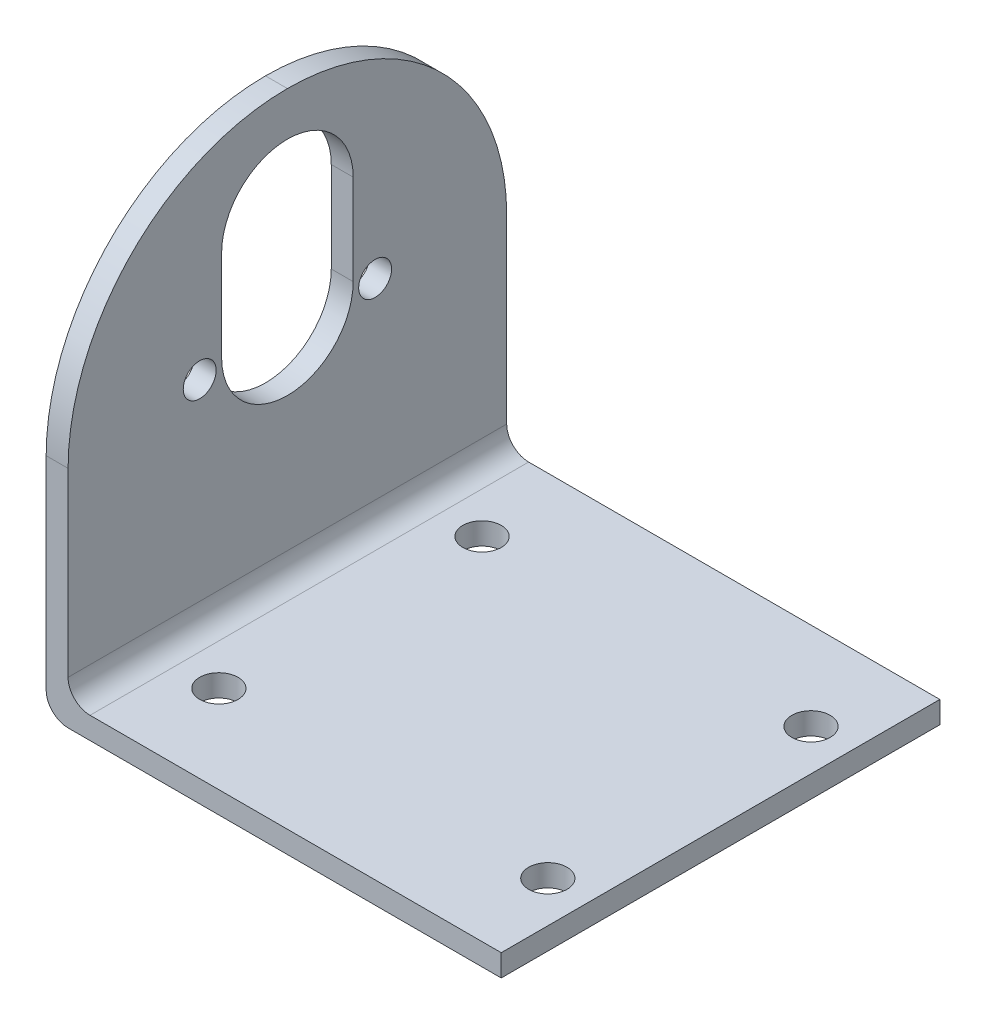
SolidWorks part; units mm, degrees
ref_plane "前视基准面" through (0, 0, 0) normal (0, 0, 1) x (1, 0, 0)
ref_plane "上视基准面" through (0, 0, 0) normal (0, 1, 0) x (1, 0, 0)
ref_plane "右视基准面" through (0, 0, 0) normal (1, 0, 0) x (0, 0, -1)
other "Configuration Table"
sketch "草图1" plane through (0, 0, 0) normal (0, 0, 1) x (1, 0, 0)
  line L0 (0, 38.5) -> (0, 2)
  line L1 (2, 0) -> (39.5, 0)
  line L2 (39.5, 0) -> (39.5, -2)
  line L3 (39.5, -2) -> (0, -2)
  line L4 (-2, 0) -> (-2, 38.5)
  line L5 (-2, 38.5) -> (0, 38.5)
  arc A0 (0, 2) -> (2, 0) centre (2, 2) ccw
  arc A1 (0, -2) -> (-2, 0) centre (0, 0) cw
  point P9 (0, 0)
  dimension "D5" = 2
  dimension "D1" = 2
  dimension "D2" = 41.5
  dimension "D3" = 2
  dimension "D4" = 40.5
extrude "凸台-拉伸1" add sketch "草图1" along normal blind 40
sketch "草图2" plane through (0, 0, 0) normal (0, 1, 0) x (1, 0, 0)
  line L0 (48.3574, -20) -> (-10.2137, -20) construction
  line L1 (20.75, 5.3835) -> (20.75, -45.303) construction
  line L2 (39.5, -40) -> (39.5, 0) construction
  line L3 (2, -40) -> (2, 0) construction
  line L4 (39.5, 0) -> (2, 0) construction
  line L5 (39.5, -40) -> (2, -40) construction
  circle A0 centre (5.75, -32) radius 1.75
  circle A1 centre (35.75, -32) radius 1.75
  circle A2 centre (5.75, -8) radius 1.75
  circle A3 centre (35.75, -8) radius 1.75
  dimension "D1" = 3.5
  dimension "D2" = 30
  dimension "D3" = 24
extrude "切除-拉伸1" cut sketch "草图2" against normal through all
sketch "草图3" plane through (0, 0, 0) normal (1, 0, 0) x (0, 0, -1)
  line L0 (-20, 43.5435) -> (-20, -10.4648) construction
  line L1 (12.7471, 20.25) -> (-55.4353, 20.25) construction
  line L2 (-20, 28.5) -> (-20, 20.25) construction
  line L3 (-14, 28.5) -> (-14, 20.25)
  line L4 (-26, 28.5) -> (-26, 20.25)
  line L5 (-40, 38.5) -> (0, 38.5) construction
  arc A0 (-14, 28.5) -> (-26, 28.5) centre (-20, 28.5) ccw
  arc A1 (-26, 20.25) -> (-14, 20.25) centre (-20, 20.25) ccw
  point P3 (-20, 24.375)
  dimension "D1" = 6
  dimension "D2" = 4
extrude "切除-拉伸2" cut sketch "草图3" against normal through all contours L4 A1 L3 A0
fillet "圆角1" radius 20 1 edges at (-1, 38.5, 40)
fillet "圆角2" radius 20 1 edges at (-1, 38.5, 0)
sketch "草图7" plane through (0, 0, 0) normal (1, 0, 0) x (0, 0, -1)
  line L0 (-20, 38.5) -> (-20, -7.3082) construction
  circle A0 centre (-28, 19.5) radius 1.5
  circle A1 centre (-12, 19.5) radius 1.5
  arc A12 (-26, 20.25) -> (-14, 20.25) centre (-20, 20.25) ccw construction
  arc A13 (-14, 28.5) -> (-26, 28.5) centre (-20, 28.5) ccw construction
  point P10 (-20, 34.5)
  point P12 (-20, 14.25)
  dimension "D1" = 8
  dimension "D2" = 15
extrude "切除-拉伸3" cut sketch "草图7" against normal through all
